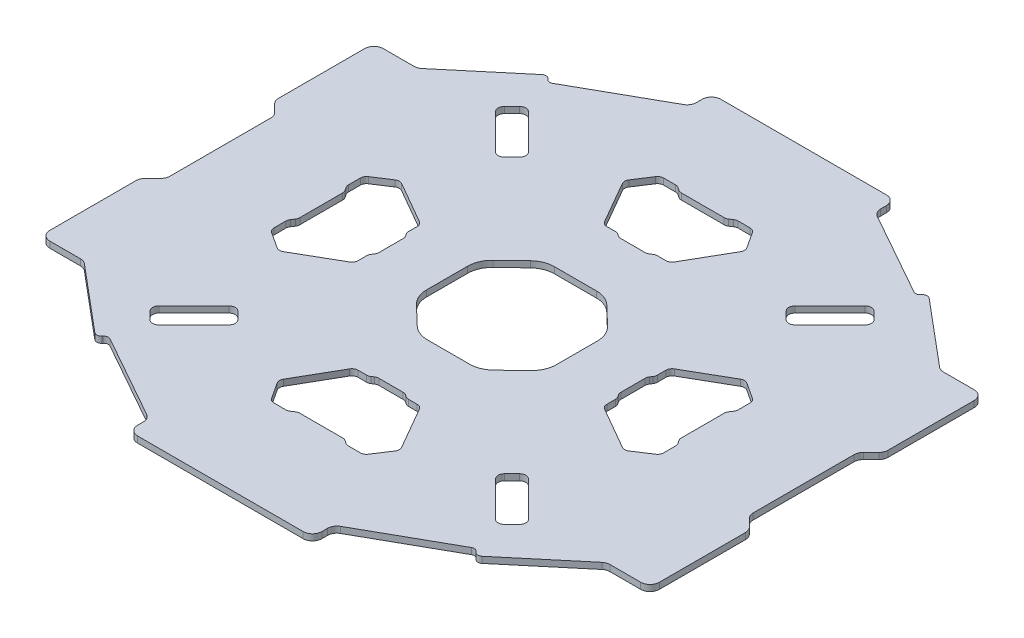
SolidWorks part; units mm, degrees
ref_plane "Piano frontale" through (0, 0, 0) normal (0, 0, 1) x (1, 0, 0)
ref_plane "Piano superiore" through (0, 0, 0) normal (0, 1, 0) x (1, 0, 0)
ref_plane "Piano destro" through (0, 0, 0) normal (1, 0, 0) x (0, 0, -1)
sketch "Schizzo3" plane through (0, 0, 0) normal (0, 1, 0) x (1, 0, 0)
  line L0 (-226.0625, 21.4509) -> (-226.0625, 53.9656)
  line L1 (-226.9412, 56.0869) -> (-229.4265, 58.5722)
  line L2 (-230.3052, 60.6935) -> (-230.3052, 88.4509)
  line L3 (-227.3052, 91.4509) -> (-217.3971, 91.4509)
  line L4 (-215.4687, 92.1528) -> (-194.4729, 109.7703)
  line L5 (-192.3597, 109.5854) -> (-192.1951, 109.3893)
  line L6 (-190.3111, 109.0459) -> (-163.2864, 124.2352)
  line L7 (-161.7563, 126.8504) -> (-161.7563, 128.7082)
  line L8 (-158.7563, 131.7082) -> (-105.3688, 131.7082)
  line L11 (-193.5625, 30.8043) -> (-193.5625, 44.6122)
  line L12 (-193.8889, 45.7071) -> (-194.5446, 46.7094)
  line L13 (-194.8709, 47.8043) -> (-194.8709, 51.6267)
  line L14 (-193.9658, 53.3003) -> (-188.7857, 56.689)
  line L15 (-186.6931, 56.7487) -> (-173.1597, 48.9588)
  line L16 (-172.1574, 47.2255) -> (-172.1574, 44.478)
  line L17 (-171.8311, 43.3831) -> (-171.3889, 42.7071)
  line L18 (-171.0625, 41.6122) -> (-171.0625, 33.8043)
  line L25 (-180.3244, 80.6668) -> (-191.6382, 91.9805)
  line L26 (-175.0211, 83.1417) -> (-177.496, 80.6668)
  line L27 (-186.3349, 97.2838) -> (-175.0211, 85.9701)
  line L28 (-191.6382, 94.809) -> (-189.1633, 97.2838)
  line L30 (-132.0625, 37.7082) -> (-218.4872, 124.1329) construction
  line L34 (-125.1586, 99.2082) -> (-138.9665, 99.2082)
  line L35 (-140.0614, 99.5346) -> (-141.0637, 100.1903)
  line L36 (-142.1586, 100.5166) -> (-145.981, 100.5166)
  line L37 (-147.6547, 99.6115) -> (-151.0433, 94.4314)
  line L38 (-151.103, 92.3388) -> (-143.3132, 78.8054)
  line L39 (-141.5798, 77.8031) -> (-138.8323, 77.8031)
  line L40 (-137.7374, 77.4768) -> (-137.0614, 77.0346)
  line L41 (-135.9665, 76.7082) -> (-128.1586, 76.7082)
  line L43 (-132.0625, 37.7082) -> (-45.6379, 124.1329) construction
  line L44 (-126.3877, 77.4768) -> (-127.0637, 77.0346)
  line L45 (-122.5453, 77.8031) -> (-125.2928, 77.8031)
  line L46 (-113.0221, 92.3388) -> (-120.8119, 78.8054)
  line L47 (-116.4704, 99.6115) -> (-113.0818, 94.4314)
  line L48 (-121.9665, 100.5166) -> (-118.1441, 100.5166)
  line L49 (-124.0637, 99.5346) -> (-123.0614, 100.1903)
  line L51 (-72.4869, 94.809) -> (-74.9618, 97.2838)
  line L52 (-77.7902, 97.2838) -> (-89.104, 85.9701)
  line L53 (-89.104, 83.1417) -> (-86.6291, 80.6668)
  line L54 (-83.8007, 80.6668) -> (-72.4869, 91.9805)
  line L55 (-93.0625, 41.6122) -> (-93.0625, 33.8043)
  line L56 (-92.294, 43.3831) -> (-92.7362, 42.7071)
  line L57 (-91.9677, 47.2255) -> (-91.9677, 44.478)
  line L58 (-77.432, 56.7487) -> (-90.9654, 48.9588)
  line L59 (-70.1593, 53.3003) -> (-75.3394, 56.689)
  line L60 (-69.2542, 47.8043) -> (-69.2542, 51.6267)
  line L61 (-70.2362, 45.7071) -> (-69.5805, 46.7094)
  line L62 (-70.5625, 30.8043) -> (-70.5625, 44.6122)
  line L63 (-102.3688, 126.8504) -> (-102.3688, 128.7082)
  line L64 (-73.814, 109.0459) -> (-100.8387, 124.2352)
  line L65 (-71.7654, 109.5854) -> (-71.93, 109.3893)
  line L66 (-48.6564, 92.1528) -> (-69.6522, 109.7703)
  line L67 (-36.8199, 91.4509) -> (-46.728, 91.4509)
  line L68 (-33.8199, 60.6935) -> (-33.8199, 88.4509)
  line L69 (-37.1839, 56.0869) -> (-34.6986, 58.5722)
  line L70 (-38.0625, 21.4509) -> (-38.0625, 53.9656)
  line L71 (-132.0625, 37.7082) -> (-45.6379, -48.7164) construction
  line L72 (-132.0625, 37.7082) -> (-218.4872, -48.7164) construction
  line L73 (-37.1839, 19.3296) -> (-34.6986, 16.8443)
  line L74 (-33.8199, 14.723) -> (-33.8199, -13.0344)
  line L75 (-36.8199, -16.0344) -> (-46.728, -16.0344)
  line L76 (-48.6564, -16.7363) -> (-69.6522, -34.3538)
  line L77 (-71.7654, -34.169) -> (-71.93, -33.9728)
  line L78 (-73.814, -33.6294) -> (-100.8387, -48.8187)
  line L79 (-102.3688, -51.4339) -> (-102.3688, -53.2918)
  line L80 (-70.2362, 29.7094) -> (-69.5805, 28.7071)
  line L81 (-69.2542, 27.6122) -> (-69.2542, 23.7898)
  line L82 (-70.1593, 22.1161) -> (-75.3394, 18.7275)
  line L83 (-77.432, 18.6678) -> (-90.9654, 26.4576)
  line L84 (-91.9677, 28.191) -> (-91.9677, 30.9385)
  line L85 (-92.294, 32.0334) -> (-92.7362, 32.7094)
  line L86 (-83.8007, -5.2503) -> (-72.4869, -16.5641)
  line L87 (-89.104, -7.7252) -> (-86.6291, -5.2503)
  line L88 (-77.7902, -21.8674) -> (-89.104, -10.5536)
  line L89 (-72.4869, -19.3925) -> (-74.9618, -21.8674)
  line L90 (-124.0637, -24.1181) -> (-123.0614, -24.7738)
  line L91 (-121.9665, -25.1001) -> (-118.1441, -25.1001)
  line L92 (-116.4704, -24.195) -> (-113.0818, -19.0149)
  line L93 (-113.0221, -16.9223) -> (-120.8119, -3.3889)
  line L94 (-122.5453, -2.3866) -> (-125.2928, -2.3866)
  line L95 (-126.3877, -2.0603) -> (-127.0637, -1.6181)
  line L96 (-132.0625, 37.7082) -> (-132.0625, 168.4992) construction
  line L97 (-135.9665, -1.2918) -> (-128.1586, -1.2918)
  line L98 (-137.7374, -2.0603) -> (-137.0614, -1.6181)
  line L99 (-141.5798, -2.3866) -> (-138.8323, -2.3866)
  line L100 (-151.103, -16.9223) -> (-143.3132, -3.3889)
  line L101 (-147.6547, -24.195) -> (-151.0433, -19.0149)
  line L102 (-142.1586, -25.1001) -> (-145.981, -25.1001)
  line L103 (-140.0614, -24.1181) -> (-141.0637, -24.7738)
  line L104 (-125.1586, -23.7918) -> (-138.9665, -23.7918)
  line L105 (-191.6382, -19.3925) -> (-189.1633, -21.8674)
  line L106 (-186.3349, -21.8674) -> (-175.0211, -10.5536)
  line L107 (-175.0211, -7.7252) -> (-177.496, -5.2503)
  line L108 (-180.3244, -5.2503) -> (-191.6382, -16.5641)
  line L109 (-171.8311, 32.0334) -> (-171.3889, 32.7094)
  line L110 (-172.1574, 28.191) -> (-172.1574, 30.9385)
  line L111 (-186.6931, 18.6678) -> (-173.1597, 26.4576)
  line L112 (-193.9658, 22.1161) -> (-188.7857, 18.7275)
  line L113 (-194.8709, 27.6122) -> (-194.8709, 23.7898)
  line L114 (-193.8889, 29.7094) -> (-194.5446, 28.7071)
  line L115 (-158.7563, -56.2918) -> (-105.3688, -56.2918)
  line L116 (-161.7563, -51.4339) -> (-161.7563, -53.2918)
  line L117 (-190.3111, -33.6294) -> (-163.2864, -48.8187)
  line L118 (-192.3597, -34.169) -> (-192.1951, -33.9728)
  line L119 (-215.4687, -16.7363) -> (-194.4729, -34.3538)
  line L120 (-227.3052, -16.0344) -> (-217.3971, -16.0344)
  line L121 (-230.3052, 14.723) -> (-230.3052, -13.0344)
  line L122 (-226.9412, 19.3296) -> (-229.4265, 16.8443)
  line L123 (-132.0625, 168.4992) -> (-132.0625, -119.8545) construction
  line L124 (-132.0625, 37.7082) -> (44.6904, 37.7082) construction
  line L125 (44.6904, 37.7082) -> (-300.9787, 37.7082) construction
  line L127 (-152.9671, 31.1216) -> (-152.9671, 44.2949)
  line L128 (-150.5029, 50.0702) -> (-144.3835, 55.9358)
  line L129 (-138.8476, 58.1605) -> (-125.2775, 58.1605)
  line L131 (-113.6222, 50.0702) -> (-119.7416, 55.9358)
  line L132 (-111.158, 31.1216) -> (-111.158, 44.2949)
  line L133 (-150.5029, 25.3463) -> (-144.3835, 19.4806)
  line L134 (-113.6222, 25.3463) -> (-119.7416, 19.4806)
  line L135 (-138.8476, 17.256) -> (-125.2775, 17.256)
  arc A0 (-161.7563, 128.7082) -> (-158.7563, 131.7082) centre (-158.7563, 128.7082) cw
  arc A1 (-163.2864, 124.2352) -> (-161.7563, 126.8504) centre (-164.7563, 126.8504) ccw
  arc A2 (-217.3971, 91.4509) -> (-215.4687, 92.1528) centre (-217.3971, 94.4509) ccw
  arc A3 (-230.3052, 88.4509) -> (-227.3052, 91.4509) centre (-227.3052, 88.4509) cw
  arc A4 (-226.0625, 53.9656) -> (-226.9412, 56.0869) centre (-229.0625, 53.9656) ccw
  arc A5 (-229.4265, 58.5722) -> (-230.3052, 60.6935) centre (-227.3052, 60.6935) cw
  arc A6 (-192.1951, 109.3893) -> (-190.3111, 109.0459) centre (-191.046, 110.3535) ccw
  arc A7 (-194.4729, 109.7703) -> (-192.3597, 109.5854) centre (-193.5087, 108.6213) cw
  arc A8 (-175.0211, 83.1417) -> (-175.0211, 85.9701) centre (-176.4354, 84.5559) ccw
  arc A9 (-180.3244, 80.6668) -> (-177.496, 80.6668) centre (-178.9102, 82.0811) ccw
  arc A10 (-186.3349, 97.2838) -> (-189.1633, 97.2838) centre (-187.7491, 95.8696) ccw
  arc A11 (-191.6382, 91.9805) -> (-191.6382, 94.809) centre (-190.2239, 93.3948) cw
  arc A12 (-171.3889, 42.7071) -> (-171.0625, 41.6122) centre (-173.0625, 41.6122) cw
  arc A13 (-172.1574, 44.478) -> (-171.8311, 43.3831) centre (-170.1574, 44.478) ccw
  arc A14 (-173.1597, 48.9588) -> (-172.1574, 47.2255) centre (-174.1574, 47.2255) cw
  arc A15 (-188.7857, 56.689) -> (-186.6931, 56.7487) centre (-187.6908, 55.0153) cw
  arc A16 (-193.5625, 44.6122) -> (-193.8889, 45.7071) centre (-195.5625, 44.6122) ccw
  arc A17 (-194.5446, 46.7094) -> (-194.8709, 47.8043) centre (-192.8709, 47.8043) cw
  arc A18 (-194.8709, 51.6267) -> (-193.9658, 53.3003) centre (-192.8709, 51.6267) cw
  arc A19 (-137.0614, 77.0346) -> (-135.9665, 76.7082) centre (-135.9665, 78.7082) ccw
  arc A20 (-138.8323, 77.8031) -> (-137.7374, 77.4768) centre (-138.8323, 75.8031) cw
  arc A21 (-143.3132, 78.8054) -> (-141.5798, 77.8031) centre (-141.5798, 79.8031) ccw
  arc A22 (-138.9665, 99.2082) -> (-140.0614, 99.5346) centre (-138.9665, 101.2082) cw
  arc A23 (-141.0637, 100.1903) -> (-142.1586, 100.5166) centre (-142.1586, 98.5166) ccw
  arc A24 (-145.981, 100.5166) -> (-147.6547, 99.6115) centre (-145.981, 98.5166) ccw
  arc A25 (-151.0433, 94.4314) -> (-151.103, 92.3388) centre (-149.3696, 93.3365) ccw
  arc A26 (-113.0818, 94.4314) -> (-113.0221, 92.3388) centre (-114.7555, 93.3365) cw
  arc A27 (-118.1441, 100.5166) -> (-116.4704, 99.6115) centre (-118.1441, 98.5166) cw
  arc A28 (-123.0614, 100.1903) -> (-121.9665, 100.5166) centre (-121.9665, 98.5166) cw
  arc A29 (-125.1586, 99.2082) -> (-124.0637, 99.5346) centre (-125.1586, 101.2082) ccw
  arc A30 (-120.8119, 78.8054) -> (-122.5453, 77.8031) centre (-122.5453, 79.8031) cw
  arc A31 (-125.2928, 77.8031) -> (-126.3877, 77.4768) centre (-125.2928, 75.8031) ccw
  arc A32 (-127.0637, 77.0346) -> (-128.1586, 76.7082) centre (-128.1586, 78.7082) cw
  arc A33 (-69.2542, 51.6267) -> (-70.1593, 53.3003) centre (-71.2542, 51.6267) ccw
  arc A34 (-69.5805, 46.7094) -> (-69.2542, 47.8043) centre (-71.2542, 47.8043) ccw
  arc A35 (-70.5625, 44.6122) -> (-70.2362, 45.7071) centre (-68.5625, 44.6122) cw
  arc A36 (-75.3394, 56.689) -> (-77.432, 56.7487) centre (-76.4343, 55.0153) ccw
  arc A37 (-90.9654, 48.9588) -> (-91.9677, 47.2255) centre (-89.9677, 47.2255) ccw
  arc A38 (-91.9677, 44.478) -> (-92.294, 43.3831) centre (-93.9677, 44.478) cw
  arc A39 (-92.7362, 42.7071) -> (-93.0625, 41.6122) centre (-91.0625, 41.6122) ccw
  arc A40 (-72.4869, 91.9805) -> (-72.4869, 94.809) centre (-73.9012, 93.3948) ccw
  arc A41 (-77.7902, 97.2838) -> (-74.9618, 97.2838) centre (-76.376, 95.8696) cw
  arc A42 (-83.8007, 80.6668) -> (-86.6291, 80.6668) centre (-85.2149, 82.0811) cw
  arc A43 (-89.104, 83.1417) -> (-89.104, 85.9701) centre (-87.6897, 84.5559) cw
  arc A44 (-69.6522, 109.7703) -> (-71.7654, 109.5854) centre (-70.6164, 108.6213) ccw
  arc A45 (-71.93, 109.3893) -> (-73.814, 109.0459) centre (-73.0791, 110.3535) cw
  arc A46 (-34.6986, 58.5722) -> (-33.8199, 60.6935) centre (-36.8199, 60.6935) ccw
  arc A47 (-38.0625, 53.9656) -> (-37.1839, 56.0869) centre (-35.0625, 53.9656) cw
  arc A48 (-33.8199, 88.4509) -> (-36.8199, 91.4509) centre (-36.8199, 88.4509) ccw
  arc A49 (-46.728, 91.4509) -> (-48.6564, 92.1528) centre (-46.728, 94.4509) cw
  arc A50 (-100.8387, 124.2352) -> (-102.3688, 126.8504) centre (-99.3688, 126.8504) cw
  arc A51 (-102.3688, 128.7082) -> (-105.3688, 131.7082) centre (-105.3688, 128.7082) ccw
  arc A52 (-102.3688, -53.2918) -> (-105.3688, -56.2918) centre (-105.3688, -53.2918) cw
  arc A53 (-100.8387, -48.8187) -> (-102.3688, -51.4339) centre (-99.3688, -51.4339) ccw
  arc A54 (-46.728, -16.0344) -> (-48.6564, -16.7363) centre (-46.728, -19.0344) ccw
  arc A55 (-33.8199, -13.0344) -> (-36.8199, -16.0344) centre (-36.8199, -13.0344) cw
  arc A56 (-38.0625, 21.4509) -> (-37.1839, 19.3296) centre (-35.0625, 21.4509) ccw
  arc A57 (-34.6986, 16.8443) -> (-33.8199, 14.723) centre (-36.8199, 14.723) cw
  arc A58 (-71.93, -33.9728) -> (-73.814, -33.6294) centre (-73.0791, -34.937) ccw
  arc A59 (-69.6522, -34.3538) -> (-71.7654, -34.169) centre (-70.6164, -33.2048) cw
  arc A60 (-89.104, -7.7252) -> (-89.104, -10.5536) centre (-87.6897, -9.1394) ccw
  arc A61 (-83.8007, -5.2503) -> (-86.6291, -5.2503) centre (-85.2149, -6.6646) ccw
  arc A62 (-77.7902, -21.8674) -> (-74.9618, -21.8674) centre (-76.376, -20.4531) ccw
  arc A63 (-72.4869, -16.5641) -> (-72.4869, -19.3925) centre (-73.9012, -17.9783) cw
  arc A64 (-92.7362, 32.7094) -> (-93.0625, 33.8043) centre (-91.0625, 33.8043) cw
  arc A65 (-91.9677, 30.9385) -> (-92.294, 32.0334) centre (-93.9677, 30.9385) ccw
  arc A66 (-90.9654, 26.4576) -> (-91.9677, 28.191) centre (-89.9677, 28.191) cw
  arc A67 (-75.3394, 18.7275) -> (-77.432, 18.6678) centre (-76.4343, 20.4012) cw
  arc A68 (-70.5625, 30.8043) -> (-70.2362, 29.7094) centre (-68.5625, 30.8043) ccw
  arc A69 (-69.5805, 28.7071) -> (-69.2542, 27.6122) centre (-71.2542, 27.6122) cw
  arc A70 (-69.2542, 23.7898) -> (-70.1593, 22.1161) centre (-71.2542, 23.7898) cw
  arc A71 (-127.0637, -1.6181) -> (-128.1586, -1.2918) centre (-128.1586, -3.2918) ccw
  arc A72 (-125.2928, -2.3866) -> (-126.3877, -2.0603) centre (-125.2928, -0.3866) cw
  arc A73 (-120.8119, -3.3889) -> (-122.5453, -2.3866) centre (-122.5453, -4.3866) ccw
  arc A74 (-125.1586, -23.7918) -> (-124.0637, -24.1181) centre (-125.1586, -25.7918) cw
  arc A75 (-123.0614, -24.7738) -> (-121.9665, -25.1001) centre (-121.9665, -23.1001) ccw
  arc A76 (-118.1441, -25.1001) -> (-116.4704, -24.195) centre (-118.1441, -23.1001) ccw
  arc A77 (-113.0818, -19.0149) -> (-113.0221, -16.9223) centre (-114.7555, -17.92) ccw
  arc A78 (-151.0433, -19.0149) -> (-151.103, -16.9223) centre (-149.3696, -17.92) cw
  arc A79 (-145.981, -25.1001) -> (-147.6547, -24.195) centre (-145.981, -23.1001) cw
  arc A80 (-141.0637, -24.7738) -> (-142.1586, -25.1001) centre (-142.1586, -23.1001) cw
  arc A81 (-138.9665, -23.7918) -> (-140.0614, -24.1181) centre (-138.9665, -25.7918) ccw
  arc A82 (-143.3132, -3.3889) -> (-141.5798, -2.3866) centre (-141.5798, -4.3866) cw
  arc A83 (-138.8323, -2.3866) -> (-137.7374, -2.0603) centre (-138.8323, -0.3866) ccw
  arc A84 (-137.0614, -1.6181) -> (-135.9665, -1.2918) centre (-135.9665, -3.2918) cw
  arc A85 (-194.8709, 23.7898) -> (-193.9658, 22.1161) centre (-192.8709, 23.7898) ccw
  arc A86 (-194.5446, 28.7071) -> (-194.8709, 27.6122) centre (-192.8709, 27.6122) ccw
  arc A87 (-193.5625, 30.8043) -> (-193.8889, 29.7094) centre (-195.5625, 30.8043) cw
  arc A88 (-188.7857, 18.7275) -> (-186.6931, 18.6678) centre (-187.6908, 20.4012) ccw
  arc A89 (-173.1597, 26.4576) -> (-172.1574, 28.191) centre (-174.1574, 28.191) ccw
  arc A90 (-172.1574, 30.9385) -> (-171.8311, 32.0334) centre (-170.1574, 30.9385) cw
  arc A91 (-171.3889, 32.7094) -> (-171.0625, 33.8043) centre (-173.0625, 33.8043) ccw
  arc A92 (-191.6382, -16.5641) -> (-191.6382, -19.3925) centre (-190.2239, -17.9783) ccw
  arc A93 (-186.3349, -21.8674) -> (-189.1633, -21.8674) centre (-187.7491, -20.4531) cw
  arc A94 (-180.3244, -5.2503) -> (-177.496, -5.2503) centre (-178.9102, -6.6646) cw
  arc A95 (-175.0211, -7.7252) -> (-175.0211, -10.5536) centre (-176.4354, -9.1394) cw
  arc A96 (-194.4729, -34.3538) -> (-192.3597, -34.169) centre (-193.5087, -33.2048) ccw
  arc A97 (-192.1951, -33.9728) -> (-190.3111, -33.6294) centre (-191.046, -34.937) cw
  arc A98 (-229.4265, 16.8443) -> (-230.3052, 14.723) centre (-227.3052, 14.723) ccw
  arc A99 (-226.0625, 21.4509) -> (-226.9412, 19.3296) centre (-229.0625, 21.4509) cw
  arc A100 (-230.3052, -13.0344) -> (-227.3052, -16.0344) centre (-227.3052, -13.0344) ccw
  arc A101 (-217.3971, -16.0344) -> (-215.4687, -16.7363) centre (-217.3971, -19.0344) cw
  arc A102 (-163.2864, -48.8187) -> (-161.7563, -51.4339) centre (-164.7563, -51.4339) cw
  arc A103 (-161.7563, -53.2918) -> (-158.7563, -56.2918) centre (-158.7563, -53.2918) ccw
  arc A112 (-152.9671, 44.2949) -> (-150.5029, 50.0702) centre (-144.9671, 44.2949) cw
  arc A113 (-125.2775, 58.1605) -> (-119.7416, 55.9358) centre (-125.2775, 50.1605) cw
  arc A114 (-111.158, 31.1216) -> (-113.6222, 25.3463) centre (-119.158, 31.1216) cw
  arc A115 (-138.8476, 17.256) -> (-144.3835, 19.4806) centre (-138.8476, 25.256) cw
  arc A116 (-152.9671, 31.1216) -> (-150.5029, 25.3463) centre (-144.9671, 31.1216) ccw
  arc A117 (-144.3835, 55.9358) -> (-138.8476, 58.1605) centre (-138.8476, 50.1605) cw
  arc A118 (-113.6222, 50.0702) -> (-111.158, 44.2949) centre (-119.158, 44.2949) cw
  arc A119 (-119.7416, 19.4806) -> (-125.2775, 17.256) centre (-125.2775, 25.256) cw
  point P13 (-176.2586, 81.9043)
  point P61 (-171.0625, 42.2082)
  point P64 (-172.1574, 43.8819)
  point P67 (-172.1574, 48.3819)
  point P70 (-187.7577, 57.3615)
  point P73 (-193.5625, 45.2082)
  point P76 (-194.8709, 47.2082)
  point P79 (-194.8709, 52.7082)
  point P82 (-136.5625, 76.7082)
  point P85 (-138.2362, 77.8031)
  point P88 (-142.7362, 77.8031)
  point P91 (-139.5625, 99.2082)
  point P94 (-141.5625, 100.5166)
  point P97 (-147.0625, 100.5166)
  point P100 (-151.7158, 93.4034)
  point P183 (-112.4093, 93.4034)
  point P184 (-117.0625, 100.5166)
  point P185 (-122.5625, 100.5166)
  point P186 (-124.5625, 99.2082)
  point P187 (-121.3889, 77.8031)
  point P188 (-125.8889, 77.8031)
  point P189 (-127.5625, 76.7082)
  point P190 (-69.2542, 52.7082)
  point P191 (-69.2542, 47.2082)
  point P192 (-70.5625, 45.2082)
  point P193 (-76.3674, 57.3615)
  point P194 (-91.9677, 48.3819)
  point P195 (-91.9677, 43.8819)
  point P196 (-93.0625, 42.2082)
  point P197 (-87.8665, 81.9043)
  point P357 (-142.0625, 58.1605)
  point P359 (-87.8665, -6.4878)
  point P360 (-93.0625, 33.2082)
  point P361 (-91.9677, 31.5346)
  point P362 (-91.9677, 27.0346)
  point P363 (-76.3674, 18.055)
  point P364 (-70.5625, 30.2082)
  point P365 (-69.2542, 28.2082)
  point P366 (-69.2542, 22.7082)
  point P367 (-127.5625, -1.2918)
  point P368 (-125.8889, -2.3866)
  point P369 (-121.3889, -2.3866)
  point P370 (-124.5625, -23.7918)
  point P371 (-122.5625, -25.1001)
  point P372 (-117.0625, -25.1001)
  point P373 (-112.4093, -17.9869)
  point P374 (-151.7158, -17.9869)
  point P375 (-147.0625, -25.1001)
  point P376 (-141.5625, -25.1001)
  point P377 (-139.5625, -23.7918)
  point P378 (-142.7362, -2.3866)
  point P379 (-138.2362, -2.3866)
  point P380 (-136.5625, -1.2918)
  point P381 (-194.8709, 22.7082)
  point P382 (-194.8709, 28.2082)
  point P383 (-193.5625, 30.2082)
  point P384 (-187.7577, 18.055)
  point P385 (-172.1574, 27.0346)
  point P386 (-172.1574, 31.5346)
  point P387 (-171.0625, 33.2082)
  point P388 (-176.2586, -6.4878)
  point P394 (-152.9671, 47.7082)
  point P397 (-152.9671, 27.7082)
  point P400 (-142.0625, 17.256)
  point P403 (-122.0625, 17.256)
  point P406 (-111.158, 27.7082)
  point P409 (-111.158, 47.7082)
  point P412 (-122.0625, 58.1605)
  dimension "D2" = 3
  dimension "D3" = 1.5
  dimension "D4" = 2
  dimension "D5" = 2
  dimension "D6" = 2
  dimension "D7" = 8
  dimension "D8" = 8
extrude "Estrusione-Estrusione1" add sketch "Schizzo3" along normal blind 2
ref_point "Punto1"
ref_point "Punto2"
ref_point "Punto3"
ref_point "Punto4"
ref_axis "Assi1" through (-193.5625, 1, -37.7082) along (1, 0, 0)
ref_axis "Assi2" through (-132.0625, 1, -58.1605) along (0, 0, 1)
ref_plane "Piano1" through (-132.0625, 0, 0) normal (-1, 0, 0) x (0, 0, 1)
ref_plane "Piano2" through (0, 0, -37.7082) normal (0, 0, 1) x (1, 0, 0)
